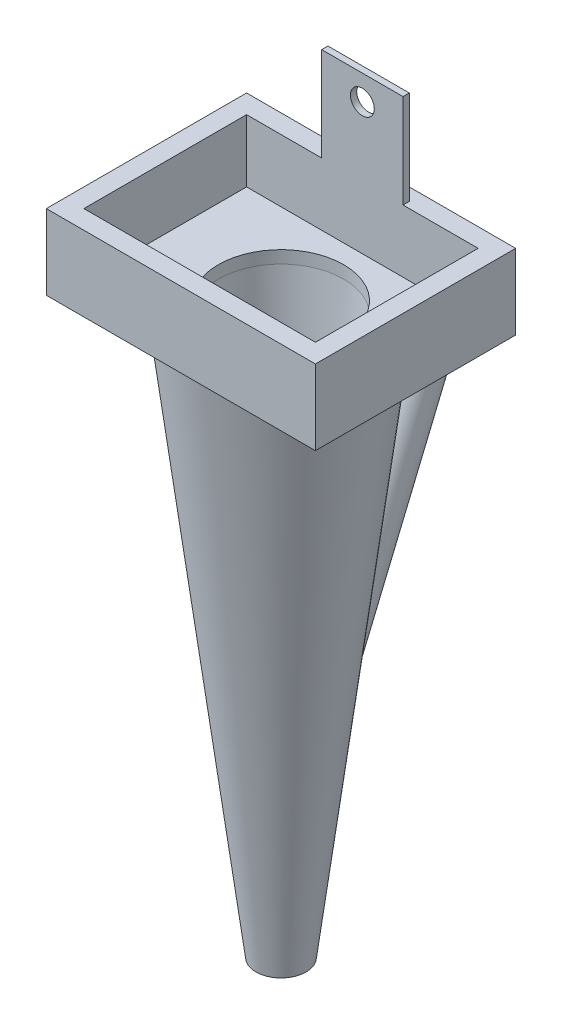
SolidWorks part; units mm, degrees
ref_plane "Front Plane" through (0, 0, 0) normal (0, 0, 1) x (1, 0, 0)
ref_plane "Top Plane" through (0, 0, 0) normal (0, 1, 0) x (1, 0, 0)
ref_plane "Right Plane" through (0, 0, 0) normal (1, 0, 0) x (0, 0, -1)
sketch "Sketch1" plane through (0, 0, 0) normal (0, 1, 0) x (1, 0, 0)
  line L1 (0, 0) -> (37, 0)
  line L2 (0, 0) -> (0, 26)
  line L3 (0, 26) -> (37, 26)
  line L4 (37, 0) -> (37, 26)
  line L5 (-3, -3) -> (40, -3)
  line L6 (-3, -3) -> (-3, 29)
  line L7 (-3, 29) -> (40, 29)
  line L8 (40, -3) -> (40, 29)
  dimension "D1" = 26
  dimension "D2" = 37
  dimension "D3" = 3
  dimension "D4" = 3
  dimension "D5" = 3
  dimension "D6" = 3
extrude "Boss-Extrude1" add sketch "Sketch1" along normal blind 10
sketch "Sketch2" plane through (0, 10, 0) normal (0, 1, 0) x (1, 0, 0)
  line L0 (37, 26) -> (0, 26) construction
  line L1 (25, 26) -> (12, 26)
  line L2 (25, 26) -> (25, 27)
  line L3 (25, 27) -> (12, 27)
  line L4 (12, 26) -> (12, 27)
  line L5 (40, -3) -> (40, 29) construction
  line L6 (-3, 29) -> (-3, -3) construction
  dimension "D1" = 1
  dimension "D2" = 15
  dimension "D3" = 15
extrude "Boss-Extrude2" add sketch "Sketch2" along normal blind 15
sketch "Sketch3" plane through (0, 0, -27) normal (0, 0, -1) x (-1, 0, 0)
  line L0 (-25, 25) -> (-12, 25) construction
  line L1 (-25, 25) -> (-25, 10) construction
  circle A0 centre (-18.5, 21) radius 1.905
  dimension "D1" = 3.81
  dimension "D2" = 4
  dimension "D3" = 6.5
extrude "Cut-Extrude1" cut sketch "Sketch3" against normal up to next
sketch "Sketch4" plane through (0, 0, 0) normal (0, -1, 0) x (1, 0, 0)
  line L1 (40, -29) -> (-3, -29)
  line L2 (40, -29) -> (40, 3)
  line L3 (40, 3) -> (-3, 3)
  line L4 (-3, -29) -> (-3, 3)
extrude "Boss-Extrude3" add sketch "Sketch4" along normal blind 2
sketch "Sketch5" plane through (0, -2, 0) normal (0, -1, 0) x (1, 0, 0)
  line L0 (-3, -29) -> (40, -29) construction
  line L2 (-3, 3) -> (-3, -29) construction
  circle A0 centre (18.5, -13) radius 10
  dimension "D1" = 16
  dimension "D2" = 21.5
extrude "Cut-Extrude2" cut sketch "Sketch5" against normal up to next
sketch "Sketch8" plane through (0, -2, 0) normal (0, -1, 0) x (1, 0, 0)
  line L0 (-3, -13) -> (40, -13) construction
  line L1 (-3, 3) -> (-3, -29) construction
  line L2 (40, -29) -> (40, 3) construction
  point P0 (18.5, -13)
ref_plane "Plane1" through (0, 0, -13) normal (0, 0, 1) x (1, 0, 0)
sketch "Sketch9" plane through (0, 0, -13) normal (0, 0, 1) x (1, 0, 0)
  line L0 (28.5, -2) -> (21.5, -90.9)
  line L1 (21.5, -90.9) -> (22.5, -90.9)
  line L2 (22.5, -90.9) -> (33.5, -2)
  line L3 (33.5, -2) -> (28.5, -2)
  line L4 (-3, -2) -> (40, -2) construction
  dimension "D1" = 1
  dimension "D2" = 3
  dimension "D3" = 88.9
  dimension "D4" = 5
ref_axis "Axis1" through (18.5, -2, -13) along (0, -1, 0)
revolve "Revolve1" add sketch "Sketch9" angle 360 about axis through (18.5, -2, -13) along (0, -1, 0)
sketch "Sketch11" plane through (-3, 0, 0) normal (-1, 0, 0) x (0, 0, 1)
  circle A0 centre (-16.2172, -43.6109) radius 3.175
ref_plane "Plane2" through (18.5, 0, 0) normal (-1, 0, 0) x (0, -1, 0)
sketch "Sketch12" plane through (18.5, 0, 0) normal (-1, 0, 0) x (0, -1, 0)
  line L0 (19.1086, -35.4998) -> (51.8373, -21.8334) construction
  line L2 (2, -28) -> (90.9, -17) construction
  line L3 (2, -28) -> (90.9, -17) construction
  point P2 (19.1086, -35.4998)
  point P3 (51.8373, -21.8334)
ref_axis "Axis2" through (18.5, -19.1086, -35.4998) along (0, -0.9228, 0.3853)
ref_plane "Plane3" through (18.5, -19.1086, -35.4998) normal (0, -0.9228, 0.3853) x (-1, 0, 0)
sketch "Sketch14" plane through (18.5, -19.1086, -35.4998) normal (0, -0.9228, 0.3853) x (-1, 0, 0)
  circle A0 centre (0.3057, 0) radius 3.4925
  dimension "D1" = 6.985
extrude "Boss-Extrude4" add sketch "Sketch14" along normal blind 45
sketch "Sketch16" plane through (0, -3.6488, 1.5236) normal (0, 0.9228, -0.3853) x (1, 0, 0)
  circle A0 centre (18.1943, 40.1215) radius 1.9925
  circle A1 centre (18.1943, 40.1215) radius 3.4925 construction
  dimension "D1" = 1.5
extrude "Cut-Extrude3" cut sketch "Sketch16" against normal blind 50
